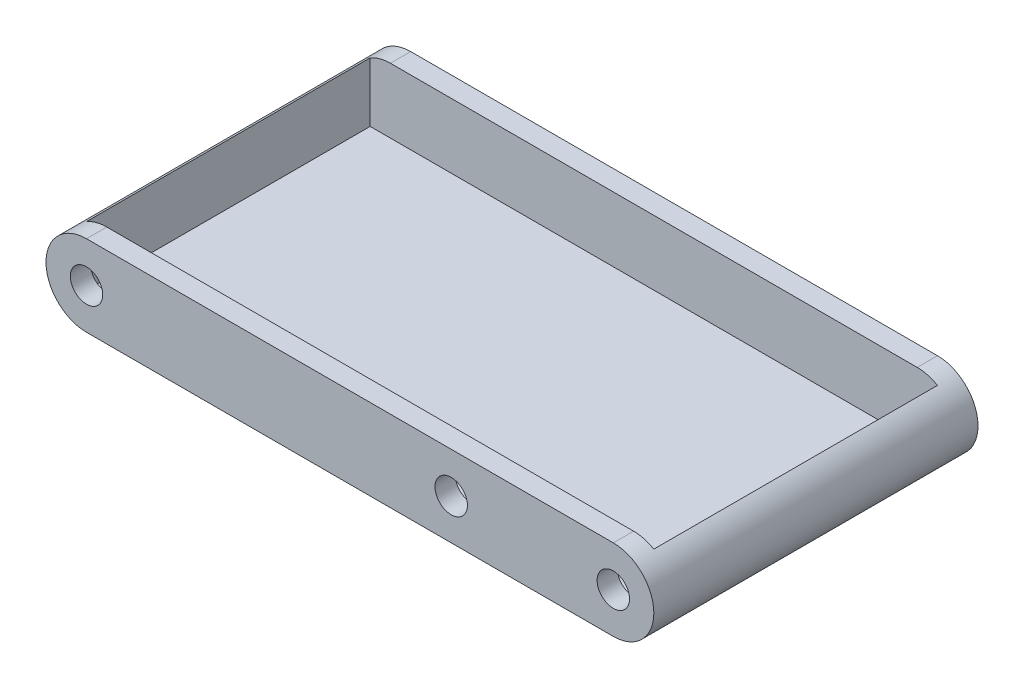
SolidWorks part; units mm, degrees
ref_plane "Front Plane" through (0, 0, 0) normal (0, 0, 1) x (1, 0, 0)
ref_plane "Top Plane" through (0, 0, 0) normal (0, 1, 0) x (1, 0, 0)
ref_plane "Right Plane" through (0, 0, 0) normal (1, 0, 0) x (0, 0, -1)
sketch "Sketch1" plane through (0, 0, 0) normal (0, 0, 1) x (1, 0, 0)
  line L0 (-65, 10) -> (65, 10)
  line L1 (-65, -10) -> (65, -10)
  line L2 (0, 10) -> (0, -10) construction
  arc A0 (65, -10) -> (65, 10) centre (65, 0) ccw
  arc A1 (-65, 10) -> (-65, -10) centre (-65, 0) ccw
  point P2 (0, 0)
  dimension "D1" = 130
  dimension "D2" = 20
extrude "Boss-Extrude1" add sketch "Sketch1" against normal blind 40 and the other way blind 40
sketch "Sketch2" plane through (0, 10, 0) normal (0, 1, 0) x (1, 0, 0)
  line L0 (-70, 35) -> (-70, -35)
  line L1 (-75, 40) -> (75, 40) construction
  line L2 (-75, 40) -> (-75, -40) construction
  line L3 (-75, -40) -> (75, -40) construction
  line L4 (75, 40) -> (75, -40) construction
  line L5 (-70, -35) -> (70, -35)
  line L6 (70, 35) -> (70, -35)
  line L7 (-70, 35) -> (70, 35)
  dimension "D1" = 5
extrude "Cut-Extrude1" cut sketch "Sketch2" against normal blind 16 contours L7 L6 L5 L0
sketch "Sketch3" plane through (0, 0, 40) normal (0, 0, 1) x (1, 0, 0)
  circle A0 centre (65, 0) radius 4
  arc A1 (65, -10) -> (65, 10) centre (65, 0) ccw construction
  circle A2 centre (-65, 0) radius 4
  arc A3 (-65, 10) -> (-65, -10) centre (-65, 0) ccw construction
  circle A4 centre (25, 0) radius 4
  dimension "D1" = 8
  dimension "D2" = 8
  dimension "D4" = 8
  dimension "D3" = 40
extrude "Cut-Extrude2" cut sketch "Sketch3" against normal up to surface (5 mm away) up to face at (0, 4.3298, 35)
